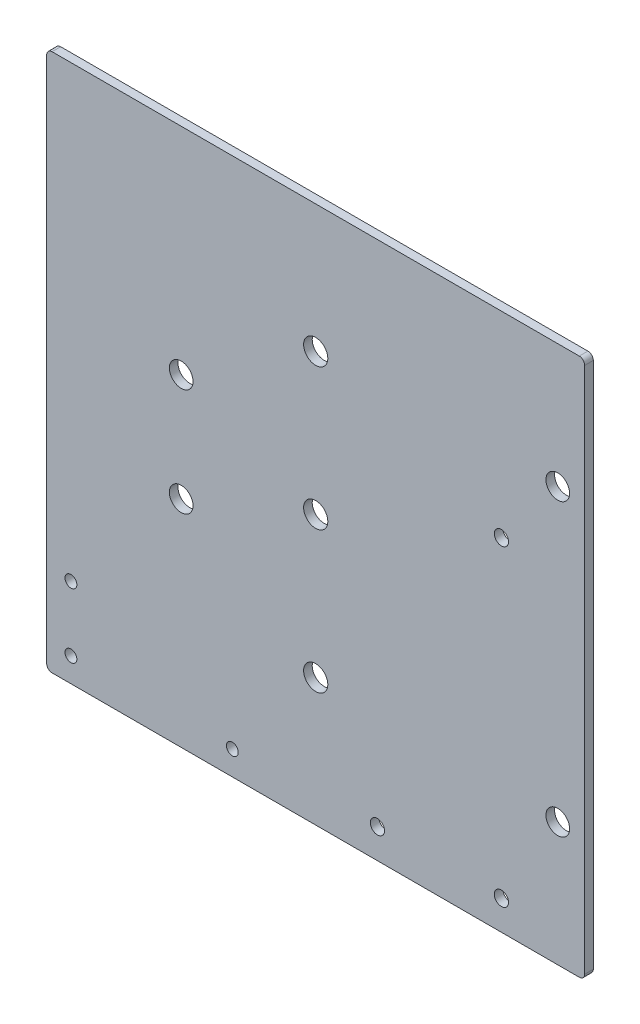
SolidWorks part; units mm, degrees
material "Copper"
ref_plane "Front Plane" through (0, 0, 0) normal (0, 0, 1) x (1, 0, 0)
ref_plane "Top Plane" through (0, 0, 0) normal (0, 1, 0) x (1, 0, 0)
ref_plane "Right Plane" through (0, 0, 0) normal (1, 0, 0) x (0, 0, -1)
sketch "Sketch1" plane through (0, 0, 0) normal (0, 0, 1) x (1, 0, 0)
  line L1 (-50, -50) -> (50, -50)
  line L2 (-50, -50) -> (-50, 50)
  line L3 (-50, 50) -> (50, 50)
  line L4 (50, -50) -> (50, 50)
  line L5 (-50, -50) -> (50, 50) construction
  line L6 (-50, 50) -> (50, -50) construction
  dimension "D1" = 100
extrude "Boss-Extrude1" add sketch "Sketch1" along normal blind 1.6
sketch "Sketch2" [suppressed] plane through (0, 0, 1.6) normal (0, 0, 1) x (1, 0, 0)
  circle A0 centre (0, 0) radius 50
  line M2 (50, -50) -> (50, 50)
  line M3 (50, 50) -> (-50, 50)
  line M4 (-50, 50) -> (-50, -50)
  line M5 (-50, -50) -> (50, -50)
  dimension "D1" = 100
extrude "Cut-Extrude1" [suppressed] cut sketch "Sketch2" against normal blind 1.6 contours A0 M3 M4 | A0 M4 M5 | A0 M5 M2 | A0 M2 M3
sketch "Sketch3" plane through (0, 0, 0) normal (0, 0, -1) x (-1, 0, 0)
  circle A0 centre (0, -26.25) radius 2.2479 construction
  circle A2 centre (0, -26.25) radius 2.2479
  circle A3 centre (0, 0) radius 2.2479
  circle A4 centre (-34.525, -44.525) radius 1.325 construction
  circle A6 centre (-34.525, -44.525) radius 1.325
  circle A8 centre (0, 26.25) radius 2.2479 construction
  circle A9 centre (0, 26.25) radius 2.2479
  circle A10 centre (-45, -27) radius 2.2 construction
  circle A11 centre (-45, -27) radius 2.2
  circle A12 centre (-45, 27) radius 2.2 construction
  circle A13 centre (-45, 27) radius 2.2
  circle A14 centre (-34.525, 13.525) radius 1.325 construction
  circle A15 centre (-34.525, 13.525) radius 1.325
  circle A16 centre (15.5, -45.5) radius 1.1 construction
  circle A17 centre (15.5, -45.5) radius 1.1
  circle A18 centre (45.5, -45.5) radius 1.1 construction
  circle A19 centre (45.5, -45.5) radius 1.1
  circle A20 centre (45.5, -33.5) radius 1.1 construction
  circle A21 centre (45.5, -33.5) radius 1.1
  circle A22 centre (-11.475, -44.525) radius 1.325 construction
  circle A23 centre (-11.475, -44.525) radius 1.325
  circle A24 centre (25, -10) radius 2.2 construction
  circle A25 centre (25, -10) radius 2.2
  circle A26 centre (25, 10) radius 2.2 construction
  circle A27 centre (25, 10) radius 2.2
  dimension "D1" = 4.4958
extrude "Cut-Extrude2" cut sketch "Sketch3" against normal up to surface (1.6 mm away) up to face at (0, 0, 1.6)
sketch "Sketch4" plane through (0, 0, 1.6) normal (0, 0, 1) x (1, 0, 0)
  line L0 (38, -44.25) -> (38, -18.925) construction
  line L5 (38, -44.25) -> (38, -18.925)
  line L6 (11.75, -48) -> (34.25, -48) construction
  line L7 (11.75, -48) -> (34.25, -48)
  line L8 (8, -44.25) -> (8, 13.25) construction
  line L9 (8, -44.25) -> (8, 13.25)
  line L11 (33, -3) -> (33, -48) construction
  line L13 (34.25, 17) -> (11.75, 17)
  line L14 (38, 13.25) -> (38, -18.925)
  line L15 (-48, -48) -> (-13, -48) construction
  line L16 (-48, -48) -> (-13, -48)
  line L17 (-48, -31) -> (-48, -48) construction
  line L18 (-48, -31) -> (-48, -48)
  line L19 (-13, -40.5) -> (-13, -32.5) construction
  line L20 (-13, -40.5) -> (-13, -32.5)
  line L21 (-13, -48) -> (-13, -40.5) construction
  line L22 (-13, -48) -> (-13, -40.5)
  line L23 (-13, -32.5) -> (-13, -31) construction
  line L24 (-13, -32.5) -> (-13, -31)
  line L25 (-13, -31) -> (-48, -31) construction
  line L26 (-13, -31) -> (-48, -31)
  line L27 (-20, -34) -> (-20, -48) construction
  arc A0 (34.25, -48) -> (38, -44.25) centre (34.25, -44.25) ccw construction
  arc A1 (34.25, -48) -> (38, -44.25) centre (34.25, -44.25) ccw
  arc A2 (8, -44.25) -> (11.75, -48) centre (11.75, -44.25) ccw construction
  arc A3 (8, -44.25) -> (11.75, -48) centre (11.75, -44.25) ccw
  arc A4 (11.75, 17) -> (8, 13.25) centre (11.75, 13.25) ccw construction
  arc A5 (11.75, 17) -> (8, 13.25) centre (11.75, 13.25) ccw
  arc A6 (38, 13.25) -> (34.25, 17) centre (34.25, 13.25) ccw construction
  arc A7 (38, 13.25) -> (34.25, 17) centre (34.25, 13.25) ccw
  text T0 "Raspberry Pi Zero W" font "Century Gothic" height 2
  text T1 "Atheros" font "Century Gothic" height 2
  point P19 (-13.7758, -31)
  dimension "D1" = 5
  dimension "D2" = 20
  dimension "D3" = 3
  dimension "D4" = 7
fillet "Fillet1" radius 1 4 edges at (-50, -50, 0.8) (-50, 50, 0.8) (50, -50, 0.8) (50, 50, 0.8)
